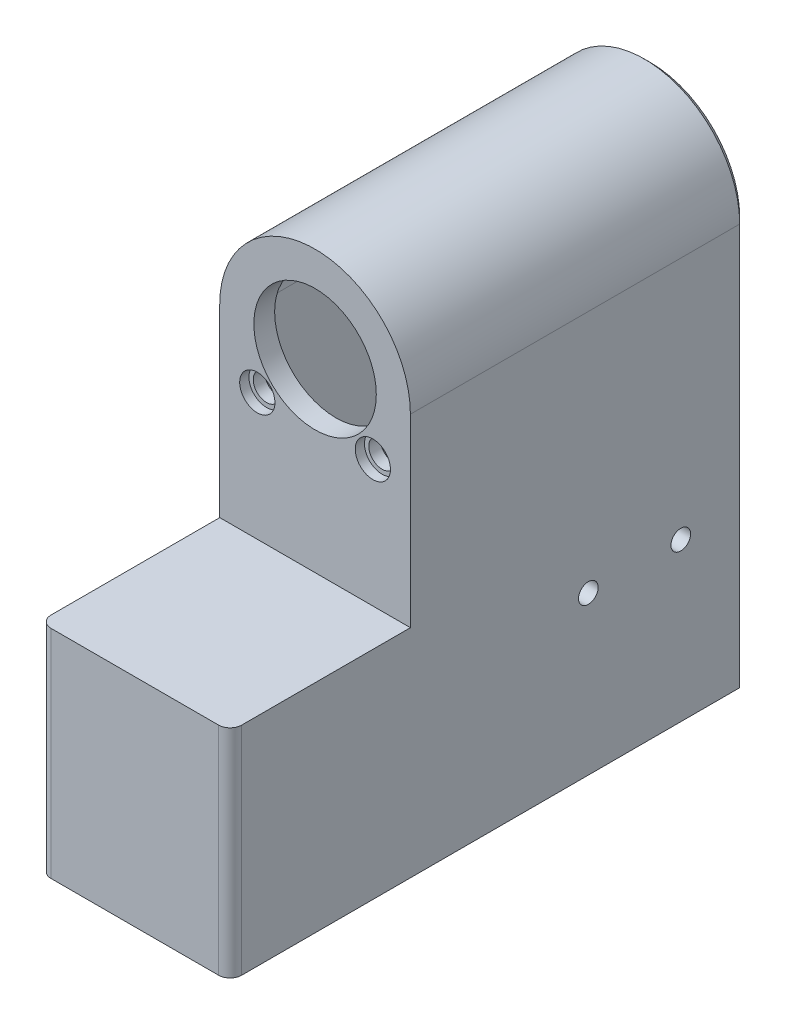
SolidWorks part; units mm, degrees
ref_plane "Front Plane" through (0, 0, 0) normal (0, 0, 1) x (1, 0, 0)
ref_plane "Top Plane" through (0, 0, 0) normal (0, 1, 0) x (1, 0, 0)
ref_plane "Right Plane" through (0, 0, 0) normal (1, 0, 0) x (0, 0, -1)
sketch "Sketch1" plane through (0, 0, 0) normal (0, 0, 1) x (1, 0, 0)
  line L0 (0, 0) -> (33, 0)
  line L1 (16.5, 0) -> (29, 0)
  line L2 (16.5, 0) -> (16.5, 9.4766)
  line L3 (4, 0) -> (4, 80.5)
  line L4 (29, 0) -> (29, 80.5)
  line L5 (0, 0) -> (0, 80.5)
  line L6 (0, 80.5) -> (4, 80.5)
  line L7 (33, 0) -> (33, 80.5)
  line L8 (33, 80.5) -> (29, 80.5)
  arc A0 (33, 80.5) -> (0, 80.5) centre (16.5, 80.5) ccw
  arc A1 (4, 80.5) -> (29, 80.5) centre (16.5, 80.5) cw
  point P5 (4, 0)
  dimension "D1" = 33
  dimension "D2" = 12.5
  dimension "D3" = 80.5
extrude "Boss-Extrude1" add sketch "Sketch1" along normal blind 71 contours L6 L5 L0 L3 | L6 A1 L8 A0 | L7 L8 L4 L0 region at (2, 40.25, 0) region at (16.5, 96.631, 0) region at (31, 40.25, 0)
sketch "Sketch2" plane through (0, 0, 71) normal (0, 0, 1) x (1, 0, 0)
  line L2 (33, 48.5) -> (0, 48.5)
  line L3 (0, 0) -> (0, 80.5) construction
  line L4 (0, 48.5) -> (0, 80.5)
  line L5 (33, 0) -> (33, 80.5) construction
  line L6 (33, 48.5) -> (33, 80.5)
  arc A0 (33, 80.5) -> (0, 80.5) centre (16.5, 80.5) ccw construction
  arc A1 (33, 80.5) -> (0, 80.5) centre (16.5, 80.5) ccw
  point P8 (16.5, 48.5)
extrude "Boss-Extrude2" add sketch "Sketch2" against normal blind 4
sketch "Sketch3" plane through (0, 0, 67) normal (0, 0, -1) x (-1, 0, 0)
  line L0 (-4, 48.5) -> (-29, 48.5) construction
  line L1 (-4, 48.5) -> (-29, 48.5)
  line L3 (-29, 44.5) -> (-4, 44.5)
  line L5 (0, 0) -> (0, 80.5) construction
  line L6 (0, 0) -> (0, 48.5)
  line L7 (-4, 48.5) -> (0, 48.5)
  line L8 (0, 0) -> (-3.8379, 0)
  line L9 (-4, 44.5) -> (-3.8379, 0)
  line L10 (-16.5, 44.5) -> (-16.5, 41.0104)
  line L11 (-33, 0) -> (-33, 48.5)
  line L12 (-29, 48.5) -> (-33, 48.5)
  line L13 (-29, 44.5) -> (-29.1621, 0)
  line L14 (-33, 0) -> (-29.1621, 0)
  line M8 (-29, 48.5) -> (-4, 48.5)
extrude "Boss-Extrude3" add sketch "Sketch3" against normal blind 34.2 contours L11 L14 L13 L3 L9 L8 L6 L7 L12 M8 region at (2, 47.9134, 67)
sketch "Sketch4" plane through (0, 0, 0) normal (0, 0, -1) x (-1, 0, 0)
  line L6 (-4, 80.5) -> (-4, 0)
  line L7 (-4, 0) -> (0, 0)
  line L8 (0, 0) -> (0, 80.5)
  line L9 (-33, 80.5) -> (-33, 0)
  line L10 (-33, 0) -> (-29, 0)
  line L11 (-29, 0) -> (-29, 80.5)
  line L12 (-4, 80.5) -> (-4, 0)
  line L13 (-4, 0) -> (0, 0)
  line L14 (0, 0) -> (0, 80.5)
  line L15 (-33, 80.5) -> (-33, 0)
  line L16 (-33, 0) -> (-29, 0)
  line L17 (-29, 0) -> (-29, 80.5)
  arc A2 (0, 80.5) -> (-33, 80.5) centre (-16.5, 80.5) ccw
  arc A3 (-4, 80.5) -> (-29, 80.5) centre (-16.5, 80.5) ccw
  arc A4 (0, 80.5) -> (-33, 80.5) centre (-16.5, 80.5) ccw
  arc A5 (-4, 80.5) -> (-29, 80.5) centre (-16.5, 80.5) ccw
  dimension "D1" = 0
extrude "Cut-Extrude1" cut sketch "Sketch4" against normal blind 13
sketch "Sketch5" plane through (0, 0, 71) normal (0, 0, 1) x (1, 0, 0)
  line L0 (0, 80.5) -> (33, 80.5)
  circle A0 centre (16.5, 80.5) radius 10
  dimension "D1" = 20
extrude "Cut-Extrude2" cut sketch "Sketch5" against normal blind 13 contours L0 A0 | L0 A0 region at (16.5, 84.7441, 71) region at (16.5, 76.2559, 71)
sketch "Sketch6" plane through (0, 0, 71) normal (0, 0, 1) x (1, 0, 0)
  line L0 (16.5, 70.5) -> (16.5, 73.1374)
  line L1 (16.5, 70.5) -> (33, 70.5)
  line L2 (33, 48.5) -> (33, 80.5) construction
  circle A0 centre (26.5, 70.5) radius 1.7
  circle A1 centre (6.5, 70.5) radius 1.7
  dimension "D2" = 3.4
  dimension "D1" = 6.5
extrude "Cut-Extrude3" cut sketch "Sketch6" against normal blind 13 contours A1 | L1 A0 | L1 A0 region at (26.5, 71.2215, 71) region at (26.5, 69.7785, 71) region at (6.5, 70.5, 71)
sketch "Sketch7" plane through (0, 0, 71) normal (0, 0, 1) x (1, 0, 0)
  circle A0 centre (6.5, 70.5) radius 3.25
  circle A1 centre (26.5, 70.5) radius 3.25
  dimension "D1" = 6.5
extrude "Cut-Extrude4" cut sketch "Sketch7" against normal blind 2.5
sketch "Sketch9" plane through (0, 0, 0) normal (0, -1, 0) x (1, 0, 0)
  line L0 (29.1621, 101.2) -> (29.1621, 71) construction
  line L1 (29.1621, 101.2) -> (29.1621, 71)
  line L2 (29.1621, 71) -> (29, 71)
  line L3 (29, 71) -> (29, 120)
  line L4 (29, 120) -> (29.1621, 101.2)
  line L6 (29, 67) -> (4, 67) construction
  line L7 (29, 67) -> (4, 67)
  line L8 (16.5, 67) -> (16.5, 71)
  line L9 (4, 120) -> (3.8379, 101.2)
  line L10 (4, 71) -> (4, 120)
  line L11 (3.8379, 71) -> (4, 71)
  line L12 (3.8379, 101.2) -> (3.8379, 71)
extrude "Boss-Extrude4" add sketch "Sketch9" against normal up to surface (44.5 mm away) contours L4 L1 L2 L3 | L9 L12 L11 L10 up to face at (16.5, 44.5, 79.7333)
sketch "Sketch10" plane through (0, 0, 101.2) normal (0, 0, 1) x (1, 0, 0)
  line L1 (40.2439, -6.5645) -> (-5.7585, -6.5645)
  line L2 (40.2439, -6.5645) -> (40.2439, 55.1467)
  line L3 (40.2439, 55.1467) -> (-5.7585, 55.1467)
  line L4 (-5.7585, -6.5645) -> (-5.7585, 55.1467)
  line L5 (40.2439, -6.5645) -> (-5.7585, 55.1467) construction
  line L6 (40.2439, 55.1467) -> (-5.7585, -6.5645) construction
  point P0 (17.2427, 24.2911)
extrude "Cut-Extrude5" cut sketch "Sketch10" along normal blind 42
sketch "Sketch11" plane through (0, 0, 101.2) normal (0, 0, 1) x (1, 0, 0)
  line L0 (29, 0) -> (4, 0)
  line L8 (4, 44.5) -> (29, 44.5)
  line L9 (29, 44.5) -> (29, 0)
  line L10 (29, 0) -> (33, 0)
  line L11 (33, 0) -> (33, 48.5)
  line L12 (33, 48.5) -> (0, 48.5)
  line L13 (0, 48.5) -> (0, 0)
  line L14 (0, 0) -> (4, 0)
  line L15 (4, 0) -> (4, 44.5)
  line L18 (29, 0) -> (33, 0)
  line L19 (33, 0) -> (33, 48.5)
  line L20 (33, 48.5) -> (0, 48.5)
  line L21 (0, 48.5) -> (0, 0)
  line L22 (0, 0) -> (4, 0)
  dimension "D1" = 0
extrude "Boss-Extrude5" add sketch "Sketch11" along normal blind 4
sketch "Sketch12" plane through (0, 0, 0) normal (0, -1, 0) x (1, 0, 0)
  line L8 (4, 13) -> (4, 101.2)
  line L9 (4, 101.2) -> (29, 101.2)
  line L10 (29, 101.2) -> (29, 13)
  line L11 (29, 13) -> (33, 13)
  line L12 (33, 13) -> (33, 105.2)
  line L13 (33, 105.2) -> (0, 105.2)
  line L14 (0, 105.2) -> (0, 13)
  line L15 (0, 13) -> (4, 13)
  line L16 (4, 13) -> (4, 101.2)
  line L17 (4, 101.2) -> (29, 101.2)
  line L18 (29, 101.2) -> (29, 13)
  line L19 (29, 13) -> (33, 13)
  line L20 (33, 13) -> (33, 105.2)
  line L21 (33, 105.2) -> (0, 105.2)
  line L22 (0, 105.2) -> (0, 13)
  line L23 (0, 13) -> (4, 13)
  dimension "D1" = 0
extrude "Cut-Extrude6" cut sketch "Sketch12" against normal blind 10.6
sketch "Sketch13" plane through (0, 0, 0) normal (-1, 0, 0) x (0, 0, 1)
  line L0 (105.2, 10.6) -> (13, 10.6) construction
  line L1 (13, 10.6) -> (13, 80.5) construction
  circle A0 centre (40.2, 38.3) radius 1.7
  circle A1 centre (24.2, 38.3) radius 1.7
  dimension "D1" = 27.7
  dimension "D2" = 3.4
  dimension "D3" = 27.2
  dimension "D4" = 16
extrude "Cut-Extrude7" cut sketch "Sketch13" against normal up to surface (33 mm away) contours A1 | A0 up to face at (33, 46.5333, 63.0667)
sketch "Sketch14" plane through (0, 0, 101.2) normal (0, 0, -1) x (-1, 0, 0)
  line L4 (-29, 10.6) -> (-4, 10.6)
  line L5 (-4, 10.6) -> (-4, 44.5)
  line L6 (-4, 44.5) -> (-29, 44.5)
  line L7 (-29, 44.5) -> (-29, 10.6)
  line L8 (-29, 10.6) -> (-4, 10.6)
  line L9 (-4, 10.6) -> (-4, 44.5)
  line L10 (-4, 44.5) -> (-29, 44.5)
  line L11 (-29, 44.5) -> (-29, 10.6)
  dimension "D1" = 0
extrude "Boss-Extrude6" add sketch "Sketch14" along normal blind 1
sketch "Sketch15" plane through (0, 10.6, 0) normal (0, -1, 0) x (1, 0, 0)
  line L0 (29, 100.2) -> (4, 100.2) construction
  line L1 (29, 100.2) -> (4, 100.2)
  line L2 (16.5, 100.2) -> (16.5, 101.5)
  line L3 (16.5, 105.2) -> (16.5, 103.9)
  line L4 (33, 105.2) -> (0, 105.2) construction
  line L5 (16.5, 101.5) -> (6.3, 101.5)
  line L6 (16.5, 101.5) -> (26.7, 101.5)
  line L7 (26.7, 101.5) -> (26.7, 103.9)
  line L8 (26.7, 103.9) -> (6.3, 103.9)
  line L9 (6.3, 103.9) -> (6.3, 101.5)
  dimension "D1" = 1.3
  dimension "D2" = 1.3
  dimension "D3" = 10.2
  dimension "D4" = 10.2
extrude "Cut-Extrude8" cut sketch "Sketch15" against normal blind 15 contours L8 L9 L5 L6 L7 region at (16.5, 10.6, 102.7)
sketch "Sketch16" plane through (0, 10.6, 0) normal (0, -1, 0) x (1, 0, 0)
  line L1 (26.7, 103.9) -> (6.3, 103.9) construction
  line L3 (21.7, 103.9) -> (21.7, 105.2)
  line L4 (33, 105.2) -> (0, 105.2) construction
  line L5 (21.7, 105.2) -> (11.3, 105.2)
  line L6 (11.3, 105.2) -> (11.3, 103.9)
  line L7 (21.7, 103.9) -> (11.3, 103.9)
  point P0 (16.5, 103.9)
  point P2 (16.5, 105.2)
  dimension "D1" = 10.4
extrude "Cut-Extrude9" cut sketch "Sketch16" against normal up to surface (15 mm away) up to face at (16.5, 25.6, 102.7)
sketch "Sketch17" plane through (0, 25.6, 0) normal (0, -1, 0) x (1, 0, 0)
  line L8 (26.7, 103.9) -> (21.7, 103.9)
  line L9 (21.7, 103.9) -> (21.7, 105.2)
  line L10 (21.7, 105.2) -> (11.3, 105.2)
  line L11 (11.3, 105.2) -> (11.3, 103.9)
  line L12 (11.3, 103.9) -> (6.3, 103.9)
  line L13 (6.3, 103.9) -> (6.3, 101.5)
  line L14 (6.3, 101.5) -> (26.7, 101.5)
  line L15 (26.7, 101.5) -> (26.7, 103.9)
  line L16 (26.7, 103.9) -> (21.7, 103.9)
  line L17 (21.7, 103.9) -> (21.7, 105.2)
  line L18 (21.7, 105.2) -> (11.3, 105.2)
  line L19 (11.3, 105.2) -> (11.3, 103.9)
  line L20 (11.3, 103.9) -> (6.3, 103.9)
  line L21 (6.3, 103.9) -> (6.3, 101.5)
  line L22 (6.3, 101.5) -> (26.7, 101.5)
  line L23 (26.7, 101.5) -> (26.7, 103.9)
  dimension "D1" = 0
extrude "popunio rupu" add sketch "Sketch17" along normal up to surface (15 mm away) up to face at (16.5, 10.6, 80.7375)
sketch "Sketch18" plane through (0, 0, 105.2) normal (0, 0, 1) x (1, 0, 0)
  line L4 (0, 48.5) -> (0, 10.6)
  line L5 (0, 10.6) -> (33, 10.6)
  line L6 (33, 10.6) -> (33, 48.5)
  line L7 (33, 48.5) -> (0, 48.5)
  line L8 (0, 48.5) -> (0, 10.6)
  line L9 (0, 10.6) -> (33, 10.6)
  line L10 (33, 10.6) -> (33, 48.5)
  line L11 (33, 48.5) -> (0, 48.5)
  dimension "D1" = 0
extrude "sasekao za tri mm" cut sketch "Sketch18" against normal blind 3
sketch "Sketch19" plane through (0, 0, 71) normal (0, 0, 1) x (1, 0, 0)
  circle A0 centre (6.5, 70.5) radius 3.25 construction
  circle A1 centre (6.5, 70.5) radius 3.25
  circle A2 centre (6.5, 70.5) radius 3.5
  circle A4 centre (26.5, 70.5) radius 3.5
  dimension "D1" = 7
extrude "pove'ao rupe za zavrtnje" cut sketch "Sketch19" against normal up to surface (2.5 mm away) up to face at (8.2, 70.5, 68.5)
sketch "Sketch20" plane through (0, 10.6, 0) normal (0, -1, 0) x (1, 0, 0)
  line L8 (33, 13) -> (33, 102.2)
  line L9 (33, 102.2) -> (0, 102.2)
  line L10 (0, 102.2) -> (0, 13)
  line L11 (0, 13) -> (4, 13)
  line L12 (4, 13) -> (4, 100.2)
  line L13 (4, 100.2) -> (29, 100.2)
  line L14 (29, 100.2) -> (29, 13)
  line L15 (29, 13) -> (33, 13)
  line L16 (33, 13) -> (33, 102.2)
  line L17 (33, 102.2) -> (0, 102.2)
  line L18 (0, 102.2) -> (0, 13)
  line L19 (0, 13) -> (4, 13)
  line L20 (4, 13) -> (4, 100.2)
  line L21 (4, 100.2) -> (29, 100.2)
  line L22 (29, 100.2) -> (29, 13)
  line L23 (29, 13) -> (33, 13)
  dimension "D1" = 0
extrude "skratio dno" cut sketch "Sketch20" against normal blind 0.4
sketch "Sketch21" plane through (0, 44.5, 0) normal (0, -1, 0) x (1, 0, 0)
  line L4 (29, 100.2) -> (4, 100.2)
  line L5 (4, 100.2) -> (4, 67)
  line L6 (4, 67) -> (29, 67)
  line L7 (29, 67) -> (29, 100.2)
  line L8 (29, 100.2) -> (4, 100.2)
  line L9 (4, 100.2) -> (4, 67)
  line L10 (4, 67) -> (29, 67)
  line L11 (29, 67) -> (29, 100.2)
  dimension "D1" = 0
extrude "napravio malo vi[e mesta za vrh razvodnika" cut sketch "Sketch21" against normal blind 0.4
sketch "Sketch22" plane through (0, 0, 67) normal (0, 0, -1) x (-1, 0, 0)
  line L3 (-29, 44.9) -> (-4, 44.9)
  line L4 (-4, 44.9) -> (-4, 80.5)
  line L5 (-29, 80.5) -> (-29, 44.9)
  line L6 (-29, 44.9) -> (-4, 44.9)
  line L7 (-4, 44.9) -> (-4, 80.5)
  line L8 (-29, 80.5) -> (-29, 44.9)
  arc A1 (-4, 80.5) -> (-29, 80.5) centre (-16.5, 80.5) ccw
  arc A2 (-4, 80.5) -> (-29, 80.5) centre (-16.5, 80.5) ccw
  dimension "D1" = 0
extrude "skratio ceoni deo" cut sketch "Sketch22" against normal blind 0.4
sketch "Sketch23" plane through (0, 0, 13) normal (0, 0, -1) x (-1, 0, 0)
  line L0 (-29, 80.5) -> (-29, 11)
  line L1 (-29, 11) -> (-29.7, 11)
  line L2 (-29.7, 11) -> (-29.7, 80.5)
  line L3 (-16.5, 80.5) -> (-16.5, 75.0754)
  line L4 (-4, 11) -> (-3.3, 11)
  line L5 (-3.3, 11) -> (-3.3, 80.5)
  line L6 (-4, 80.5) -> (-4, 11) construction
  line L7 (-4, 80.5) -> (-4, 11)
  arc A0 (-4, 80.5) -> (-29, 80.5) centre (-16.5, 80.5) ccw construction
  arc A1 (-4, 80.5) -> (-29, 80.5) centre (-16.5, 80.5) ccw
  arc A2 (-29.7, 80.5) -> (-3.3, 80.5) centre (-16.5, 80.5) cw
  point P12 (0, 0)
  dimension "D1" = 0.7
extrude "napravio mesta za drzac 1" cut sketch "Sketch23" against normal up to surface (54.4 mm away) contours L0 L1 L2 A2 L5 L4 L7 A1 up to face at (4.8, 70.5, 67.4)
sketch "Sketch24" plane through (0, 0, 67.4) normal (0, 0, -1) x (-1, 0, 0)
  line L0 (-3.3, 80.5) -> (-3.3, 11) construction
  line L1 (-3.3, 11) -> (-4, 11) construction
  line L2 (-4, 11) -> (-4, 44.9) construction
  line L3 (-29.7, 11) -> (-29, 11) construction
  line L4 (-29.7, 80.5) -> (-29.7, 11) construction
  line L5 (-29, 11) -> (-29, 44.9) construction
  line L6 (-3.3, 44.9) -> (-3.3, 11)
  line L7 (-3.3, 11) -> (-4, 11)
  line L8 (-4, 11) -> (-4, 44.9)
  line L9 (-29.7, 11) -> (-29, 11)
  line L10 (-29.7, 44.9) -> (-29.7, 11)
  line L11 (-29, 11) -> (-29, 44.9)
  line L12 (-29.7, 44.9) -> (-29, 44.9)
  line L13 (-4, 44.9) -> (-3.3, 44.9)
extrude "napravio emsta za drzac 2" cut sketch "Sketch24" against normal up to surface (32.8 mm away) up to face at (16.5, 27.95, 100.2)
chamfer "Chamfer1" distance 1 angle 45 2 edges at (1.65, 11, 13) (31.35, 11, 13)
sketch "Sketch26" plane through (0, 0, 68.5) normal (0, 0, 1) x (1, 0, 0)
  circle A0 centre (26.5, 70.5) radius 2.3
  circle A1 centre (6.5, 70.5) radius 2.3
  dimension "D1" = 4.6
  dimension "D2" = 4.6
extrude "povecao otvor za M3" cut sketch "Sketch26" against normal up to surface (1.1 mm away) up to face at (16.5, 66, 67.4)
sketch "Sketch27" plane through (0, 0, 71) normal (0, 0, 1) x (1, 0, 0)
  circle A0 centre (16.5, 80.5) radius 10.6
  dimension "D1" = 21.2
extrude "povecao otvor za prikljucak" cut sketch "Sketch27" against normal blind 10
sketch "Sketch28" plane through (0, 0, 100.2) normal (0, 0, -1) x (-1, 0, 0)
  line L4 (-3.3, 44.9) -> (-29.7, 44.9)
  line L5 (-29.7, 44.9) -> (-29.7, 11)
  line L6 (-29.7, 11) -> (-3.3, 11)
  line L7 (-3.3, 11) -> (-3.3, 44.9)
  line L8 (-3.3, 44.9) -> (-29.7, 44.9)
  line L9 (-29.7, 44.9) -> (-29.7, 11)
  line L10 (-29.7, 11) -> (-3.3, 11)
  line L11 (-3.3, 11) -> (-3.3, 44.9)
  dimension "D1" = 0
extrude "Boss-Extrude7" add sketch "Sketch28" along normal blind 2
chamfer "oborena ivica za šaku" distance 1 angle 45 3 edges at (0, 46.25, 13) (16.5, 97, 13) (33, 46.25, 13)
sketch "Sketch29" plane through (0, 0, 68.5) normal (0, 0, 1) x (1, 0, 0)
  circle A0 centre (6.5, 70.5) radius 3.5 construction
  circle A1 centre (6.5, 70.5) radius 3.5
  circle A2 centre (6.5, 70.5) radius 2.3 construction
  circle A3 centre (6.5, 70.5) radius 2.3
  circle A4 centre (26.5, 70.5) radius 2.3 construction
  circle A5 centre (26.5, 70.5) radius 2.3
  circle A6 centre (26.5, 70.5) radius 3.5 construction
  circle A7 centre (26.5, 70.5) radius 3.5
extrude "Boss-Extrude8" add sketch "Sketch29" along normal blind 0.9
sketch "Sketch31" plane through (0, 0, 69.4) normal (0, 0, 1) x (1, 0, 0)
  circle A0 centre (6.5, 70.5) radius 3.5 construction
  circle A1 centre (6.5, 70.5) radius 3.5
  circle A2 centre (6.5, 70.5) radius 3.05
  dimension "D1" = 6.1
extrude "Boss-Extrude9" add sketch "Sketch31" along normal up to surface (1.6 mm away) up to face at (27.1, 80.5, 71)
sketch "Sketch32" plane through (0, 0, 69.4) normal (0, 0, 1) x (1, 0, 0)
  circle A0 centre (26.5, 70.5) radius 3.05
  circle A1 centre (26.5, 70.5) radius 3.5 construction
  circle A2 centre (26.5, 70.5) radius 3.5
  dimension "D1" = 6.1
extrude "Boss-Extrude10" add sketch "Sketch32" along normal up to surface (1.6 mm away) up to face at (27.1, 80.5, 71)
sketch "Sketch33" plane through (0, 0, 98.2) normal (0, 0, -1) x (-1, 0, 0)
  line L4 (-3.3, 11) -> (-3.3, 44.9)
  line L5 (-3.3, 44.9) -> (-29.7, 44.9)
  line L6 (-29.7, 44.9) -> (-29.7, 11)
  line L7 (-29.7, 11) -> (-3.3, 11)
  line L8 (-3.3, 11) -> (-3.3, 44.9)
  line L9 (-3.3, 44.9) -> (-29.7, 44.9)
  line L10 (-29.7, 44.9) -> (-29.7, 11)
  line L11 (-29.7, 11) -> (-3.3, 11)
  dimension "D1" = 0
extrude "Cut-Extrude11" cut sketch "Sketch33" against normal blind 0.6
fillet "Fillet1" radius 2 4 edges at (29.7, 27.95, 98.8) (33, 29.75, 102.2) (0, 29.75, 102.2) (3.3, 27.95, 98.8)
